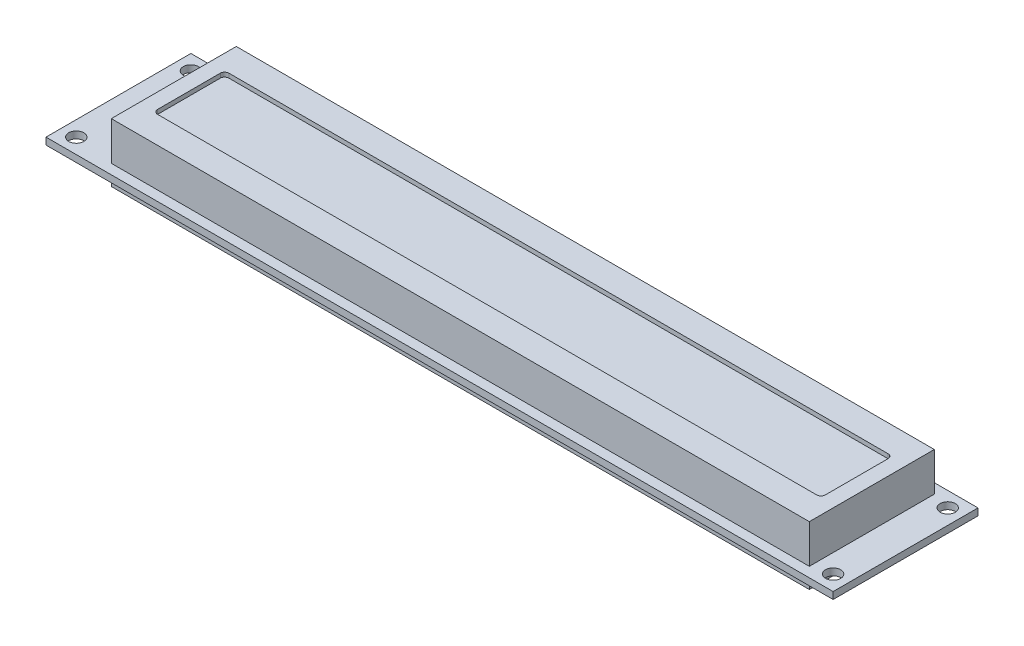
SolidWorks part; units mm, degrees
ref_plane "Front Plane" through (0, 0, 0) normal (0, 0, 1) x (1, 0, 0)
ref_plane "Top Plane" through (0, 0, 0) normal (0, 1, 0) x (1, 0, 0)
ref_plane "Right Plane" through (0, 0, 0) normal (1, 0, 0) x (0, 0, -1)
sketch "Sketch1" plane through (0, 0, 0) normal (0, 1, 0) x (1, 0, 0)
  line L1 (-80.2724, 2.9347) -> (101.7276, 2.9347)
  line L2 (-80.2724, 2.9347) -> (-80.2724, -30.5653)
  line L3 (-80.2724, -30.5653) -> (101.7276, -30.5653)
  line L4 (101.7276, 2.9347) -> (101.7276, -30.5653)
  dimension "D1" = 33.5
  dimension "D2" = 182
extrude "Boss-Extrude1" add sketch "Sketch1" along normal blind 1.6
sketch "Sketch2" plane through (0, 1.6, 0) normal (0, 1, 0) x (1, 0, 0)
  line L0 (101.7276, 2.9347) -> (-80.2724, 2.9347) construction
  line L1 (-80.2724, 2.9347) -> (-80.2724, -30.5653) construction
  circle A0 centre (-76.7724, -0.5653) radius 1.75
  dimension "D1" = 3.5
  dimension "D2" = 3.5
  dimension "D3" = 3.5
extrude "Cut-Extrude1" cut sketch "Sketch2" against normal blind 1.6
pattern_linear "LPattern1" count 2 spacing 175 along (1, 0, 0) count 2 spacing 26.5 along (0, 0, 1) of "Cut-Extrude1"
sketch "Sketch3" plane through (0, 1.6, 0) normal (0, 1, 0) x (1, 0, 0)
  line L0 (-80.2724, -30.5653) -> (101.7276, -30.5653) construction
  line L1 (-67.4724, 0.6347) -> (93.9276, 0.6347)
  line L2 (-67.4724, 0.6347) -> (-67.4724, -28.2653)
  line L3 (-67.4724, -28.2653) -> (93.9276, -28.2653)
  line L4 (93.9276, 0.6347) -> (93.9276, -28.2653)
  circle A0 centre (98.2276, -0.5653) radius 1.75 construction
  dimension "D4" = 4.3
  dimension "D1" = 28.9
  dimension "D2" = 161.4
  dimension "D3" = 2.3
extrude "Boss-Extrude2" add sketch "Sketch3" along normal blind 8.95
extrude "Boss-Extrude3" add sketch "Sketch3<2>" against normal blind 4.65
sketch "Sketch3<2>" plane through (0, 1.6, 0) normal (0, 1, 0) x (1, 0, 0) same geometry as "Sketch3"
sketch "Sketch4" plane through (0, 10.55, 0) normal (0, 1, 0) x (1, 0, 0)
  line L1 (-63.9724, -5.5653) -> (90.4276, -5.5653)
  line L2 (-63.9724, -5.5653) -> (-63.9724, -22.0653)
  line L3 (-63.9724, -22.0653) -> (90.4276, -22.0653)
  line L4 (90.4276, -5.5653) -> (90.4276, -22.0653)
  circle A0 centre (-76.7724, -0.5653) radius 1.75 construction
  circle A1 centre (98.2276, -0.5653) radius 1.75 construction
  dimension "D1" = 154.4
  dimension "D2" = 16.5
  dimension "D3" = 5
  dimension "D4" = 7.8
extrude "Cut-Extrude2" cut sketch "Sketch4" against normal blind 1
fillet "Fillet1" radius 1 1 edges at (-63.9724, 10.05, 5.5653)
fillet "Fillet2" radius 1 1 edges at (-63.9724, 10.05, 22.0653)
fillet "Fillet3" radius 1 1 edges at (90.4276, 10.05, 5.5653)
fillet "Fillet4" radius 1 1 edges at (90.4276, 10.05, 22.0653)
